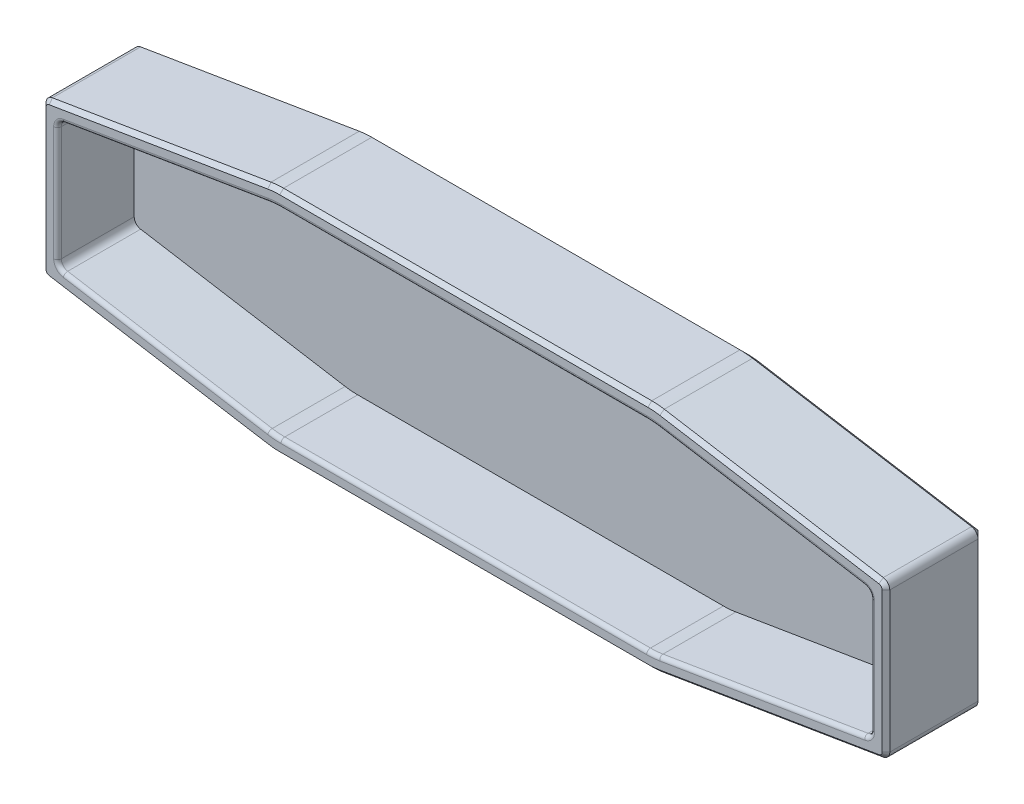
SolidWorks part; units mm, degrees
material "moto_black"
ref_plane "Front Plane" through (0, 0, 0) normal (0, 0, 1) x (1, 0, 0)
ref_plane "Top Plane" through (0, 0, 0) normal (0, 1, 0) x (1, 0, 0)
ref_plane "Right Plane" through (0, 0, 0) normal (1, 0, 0) x (0, 0, -1)
sketch "Sketch1" plane through (0, 0, 0) normal (0, 0, 1) x (1, 0, 0)
  line L12 (-24.854, 15) -> (-55, 10)
  line L14 (55, 10) -> (24.7913, 15)
  line L16 (-24.854, 15) -> (24.7913, 15)
  line L25 (0, 0) -> (4.6771, 0)
  line L26 (55, -10) -> (24.7913, -15)
  line L27 (-24.854, -15) -> (24.7913, -15)
  line L28 (-24.854, -15) -> (-55, -10)
  line L29 (-24.6892, 13) -> (-53, 8.3044)
  line L30 (-53, 8.3044) -> (-53, -8.3044)
  line L31 (-24.6892, -13) -> (-53, -8.3044)
  line L32 (-24.6892, -13) -> (24.6269, -13)
  line L33 (53, -8.3038) -> (24.6269, -13)
  line L34 (53, 8.3038) -> (53, -8.3038)
  line L35 (53, 8.3038) -> (24.6269, 13)
  line L36 (-55, 10) -> (-55, -10)
  line L37 (55, 10) -> (55, -10)
  line L38 (-24.6892, 13) -> (24.6269, 13)
  line L39 (-24.6069, 12) -> (-52, 7.4566)
  line L40 (-52, 7.4566) -> (-52, -7.4566)
  line L41 (-24.6069, -12) -> (-52, -7.4566)
  line L42 (-24.6069, -12) -> (24.5447, -12)
  line L43 (52, -7.4557) -> (24.5447, -12)
  line L44 (52, 7.4557) -> (52, -7.4557)
  line L45 (52, 7.4557) -> (24.5447, 12)
  line L46 (-24.6069, 12) -> (24.5447, 12)
  line L47 (-24.6069, 12) -> (-24.6069, -12)
  line L48 (6.6929, 12) -> (6.6929, -12)
  line L49 (-23.6069, 12) -> (-23.6069, -12)
  line L50 (-25.6069, 11.8341) -> (-25.6069, -11.8341)
  line L51 (0, 0) -> (0, 3.5519)
  line L52 (-7.6929, 12) -> (-7.6929, -12)
  line L53 (-8.6929, 12) -> (-8.6929, -12)
  line L54 (-9.6929, 12) -> (-9.6929, -12)
  line L55 (-10.6929, 12) -> (-10.6929, -12)
  line L56 (-11.6929, 12) -> (-11.6929, -12)
  line L57 (-12.6929, 12) -> (-12.6929, -12)
  line L58 (-13.6929, 12) -> (-13.6929, -12)
  line L59 (-14.6929, 12) -> (-14.6929, -12)
  line L60 (-15.6929, 12) -> (-15.6929, -12)
  line L61 (-16.6929, 12) -> (-16.6929, -12)
  line L62 (-17.6929, 12) -> (-17.6929, -12)
  line L63 (-18.6929, 12) -> (-18.6929, -12)
  line L64 (-19.6929, 12) -> (-19.6929, -12)
  line L65 (-20.6929, 12) -> (-20.6929, -12)
  line L66 (-21.6929, 12) -> (-21.6929, -12)
  line L67 (-22.6929, 12) -> (-22.6929, -12)
  line L68 (-26.6069, 11.6683) -> (-26.6069, -11.6683)
  line L69 (-27.6069, 11.5024) -> (-27.6069, -11.5024)
  line L70 (-28.6069, 11.3366) -> (-28.6069, -11.3366)
  line L71 (-29.6069, 11.1707) -> (-29.6069, -11.1707)
  line L72 (-30.6069, 11.0048) -> (-30.6069, -11.0048)
  line L73 (-31.6069, 10.839) -> (-31.6069, -10.839)
  line L74 (-32.6069, 10.6731) -> (-32.6069, -10.6731)
  line L75 (-33.6069, 10.5073) -> (-33.6069, -10.5073)
  line L76 (-34.6069, 10.3414) -> (-34.6069, -10.3414)
  line L77 (-35.6069, 10.1755) -> (-35.6069, -10.1755)
  line L78 (-36.6069, 10.0097) -> (-36.6069, -10.0097)
  line L79 (-37.6069, 9.8438) -> (-37.6069, -9.8438)
  line L80 (-38.6069, 9.678) -> (-38.6069, -9.678)
  line L81 (-39.6069, 9.5121) -> (-39.6069, -9.5121)
  line L82 (-40.6069, 9.3463) -> (-40.6069, -9.3463)
  line L83 (-41.6069, 9.1804) -> (-41.6069, -9.1804)
  line L84 (-42.6069, 9.0145) -> (-42.6069, -9.0145)
  line L85 (-43.6069, 8.8487) -> (-43.6069, -8.8487)
  line L86 (-44.6069, 8.6828) -> (-44.6069, -8.6828)
  line L87 (-45.6069, 8.517) -> (-45.6069, -8.517)
  line L88 (-46.6069, 8.3511) -> (-46.6069, -8.3511)
  line L89 (-47.6069, 8.1852) -> (-47.6069, -8.1852)
  line L90 (-48.6069, 8.0194) -> (-48.6069, -8.0194)
  line L91 (-49.6069, 7.8535) -> (-49.6069, -7.8535)
  line L92 (-50.6069, 7.6877) -> (-50.6069, -7.6877)
  line L93 (-51.6069, 7.5218) -> (-51.6069, -7.5218)
  line L94 (-6.6929, 12) -> (-6.6929, -12)
  line L95 (-5.6929, 12) -> (-5.6929, -12)
  line L96 (-4.6929, 12) -> (-4.6929, -12)
  line L97 (-3.6929, 12) -> (-3.6929, -12)
  line L98 (-2.6929, 12) -> (-2.6929, -12)
  line L99 (-1.6929, 12) -> (-1.6929, -12)
  line L100 (-0.6929, 12) -> (-0.6929, -12)
  line L101 (5.6929, 12) -> (5.6929, -12)
  line L102 (4.6929, 12) -> (4.6929, -12)
  line L103 (3.6929, 12) -> (3.6929, -12)
  line L104 (24.6069, 12) -> (-24.5447, 12)
  line L105 (-52, 7.4557) -> (-24.5447, 12)
  line L106 (-52, 7.4557) -> (-52, -7.4557)
  line L107 (-52, -7.4557) -> (-24.5447, -12)
  line L108 (24.6069, -12) -> (-24.5447, -12)
  line L109 (24.6069, -12) -> (52, -7.4566)
  line L110 (52, 7.4566) -> (52, -7.4566)
  line L111 (24.6069, 12) -> (52, 7.4566)
  line L112 (2.6929, 12) -> (2.6929, -12)
  line L113 (1.6929, 12) -> (1.6929, -12)
  line L114 (0.6929, 12) -> (0.6929, -12)
  line L115 (7.6929, 12) -> (7.6929, -12)
  line L116 (8.6929, 12) -> (8.6929, -12)
  line L117 (9.6929, 12) -> (9.6929, -12)
  line L118 (10.6929, 12) -> (10.6929, -12)
  line L119 (11.6929, 12) -> (11.6929, -12)
  line L120 (12.6929, 12) -> (12.6929, -12)
  line L121 (13.6929, 12) -> (13.6929, -12)
  line L122 (14.6929, 12) -> (14.6929, -12)
  line L123 (15.6929, 12) -> (15.6929, -12)
  line L124 (16.6929, 12) -> (16.6929, -12)
  line L125 (17.6929, 12) -> (17.6929, -12)
  line L126 (18.6929, 12) -> (18.6929, -12)
  line L127 (19.6929, 12) -> (19.6929, -12)
  line L128 (20.6929, 12) -> (20.6929, -12)
  line L129 (21.6929, 12) -> (21.6929, -12)
  line L130 (22.6929, 12) -> (22.6929, -12)
  line L131 (23.6069, 12) -> (23.6069, -12)
  line L132 (24.6069, 12) -> (24.6069, -12)
  line L133 (25.6069, 11.8341) -> (25.6069, -11.8341)
  line L134 (26.6069, 11.6683) -> (26.6069, -11.6683)
  line L135 (27.6069, 11.5024) -> (27.6069, -11.5024)
  line L136 (28.6069, 11.3366) -> (28.6069, -11.3366)
  line L137 (29.6069, 11.1707) -> (29.6069, -11.1707)
  line L138 (30.6069, 11.0048) -> (30.6069, -11.0048)
  line L139 (31.6069, 10.839) -> (31.6069, -10.839)
  line L140 (32.6069, 10.6731) -> (32.6069, -10.6731)
  line L141 (33.6069, 10.5073) -> (33.6069, -10.5073)
  line L142 (34.6069, 10.3414) -> (34.6069, -10.3414)
  line L143 (35.6069, 10.1755) -> (35.6069, -10.1755)
  line L144 (36.6069, 10.0097) -> (36.6069, -10.0097)
  line L145 (37.6069, 9.8438) -> (37.6069, -9.8438)
  line L146 (38.6069, 9.678) -> (38.6069, -9.678)
  line L147 (39.6069, 9.5121) -> (39.6069, -9.5121)
  line L148 (40.6069, 9.3463) -> (40.6069, -9.3463)
  line L149 (41.6069, 9.1804) -> (41.6069, -9.1804)
  line L150 (42.6069, 9.0145) -> (42.6069, -9.0145)
  line L151 (43.6069, 8.8487) -> (43.6069, -8.8487)
  line L152 (44.6069, 8.6828) -> (44.6069, -8.6828)
  line L153 (45.6069, 8.517) -> (45.6069, -8.517)
  line L154 (46.6069, 8.3511) -> (46.6069, -8.3511)
  line L155 (47.6069, 8.1852) -> (47.6069, -8.1852)
  line L156 (48.6069, 8.0194) -> (48.6069, -8.0194)
  line L157 (49.6069, 7.8535) -> (49.6069, -7.8535)
  line L158 (50.6069, 7.6877) -> (50.6069, -7.6877)
  line L159 (51.6069, 7.5218) -> (51.6069, -7.5218)
  point P3 (-55, 0)
  point P7 (55, 0)
  dimension "D1" = 10
  dimension "D2" = 10
  dimension "D3" = 15
  dimension "D4" = 2
  dimension "D5" = 1
  dimension "D6" = 1
  dimension "D7" = 1
  dimension "D8" = 1
  dimension "D9" = 1
  dimension "D10" = 1
  dimension "D11" = 1
  dimension "D12" = 1
  dimension "D13" = 1
  dimension "D14" = 1
  dimension "D15" = 1
  dimension "D16" = 1
  dimension "D17" = 1
  dimension "D18" = 1
  dimension "D19" = 1
  dimension "D20" = 1
  dimension "D21" = 1
  dimension "D22" = 1
  dimension "D23" = 1
  dimension "D24" = 1
  dimension "D25" = 1
  dimension "D26" = 1
  dimension "D27" = 1
  dimension "1" = 1
  dimension "D28" = 1
  dimension "D29" = 1
  dimension "D30" = 1
  dimension "D31" = 1
  dimension "D32" = 1
  dimension "D33" = 1
  dimension "D34" = 1
  dimension "D35" = 1
  dimension "D36" = 1
  dimension "D37" = 1
  dimension "D38" = 1
  dimension "D39" = 1
  dimension "D40" = 1
  dimension "D41" = 1
  dimension "D42" = 1
  dimension "D43" = 1
  dimension "D44" = 1
  dimension "D45" = 1
  dimension "D46" = 1
  dimension "D47" = 1
  dimension "D48" = 1
  dimension "D49" = 1
  dimension "D50" = 1
  dimension "D51" = 1
  dimension "D52" = 1
  dimension "D54" = 1
  dimension "D55" = 1
extrude "Boss-Extrude1" add sketch "Sketch1" against normal blind 3 contours L37 L14 L16 L12 L36 L28 L27 L26 L29 L38 L35 L34 L33 L32 L31 L30 region at (-0.0314, 13.8598, 0)
sketch "Sketch3" plane through (0, 0, 0) normal (0, 0, 1) x (1, 0, 0)
  line L44 (-53, 8.3044) -> (-53, -8.3044)
  line L45 (-53, -8.3044) -> (-24.6892, -13)
  line L46 (-24.6892, -13) -> (24.6269, -13)
  line L47 (24.6269, -13) -> (53, -8.3038)
  line L48 (53, -8.3038) -> (53, 8.3038)
  line L49 (53, 8.3038) -> (24.6269, 13)
  line L50 (24.6269, 13) -> (-24.6892, 13)
  line L51 (-24.6892, 13) -> (-53, 8.3044)
  line L52 (-53, 8.3044) -> (-53, -8.3044)
  line L53 (-53, -8.3044) -> (-24.6892, -13)
  line L54 (-24.6892, -13) -> (24.6269, -13)
  line L55 (24.6269, -13) -> (53, -8.3038)
  line L56 (53, -8.3038) -> (53, 8.3038)
  line L57 (53, 8.3038) -> (24.6269, 13)
  line L58 (24.6269, 13) -> (-24.6892, 13)
  line L59 (-24.6892, 13) -> (-53, 8.3044)
  dimension "D1" = 0
extrude "Boss-Extrude2" add sketch "Sketch3" against normal blind 3
extrude "Boss-Extrude3" add sketch "Sketch1<4>" along normal blind 10 contours L37 L14 L16 L12 L36 L28 L27 L26 L29 L38 L35 L34 L33 L32 L31 L30 region at (-0.0314, 13.8598, 0)
sketch "Sketch1<4>" plane through (0, 0, 0) normal (0, 0, 1) x (1, 0, 0) same geometry as "Sketch1"
fillet "Fillet1" radius 10 8 edges at (24.7913, -15, 3.5) (24.6269, -13, 5) (24.7913, 15, 3.5) (24.6269, 13, 5) (-24.6892, 13, 5) (-24.854, 15, 3.5) (-24.6892, -13, 5) (-24.854, -15, 3.5)
fillet "Fillet2" radius 1 8 edges at (55, 10, 3.5) (55, -10, 3.5) (53, -8.3038, 5) (53, 8.3038, 5) (-53, 8.3044, 5) (-55, 10, 3.5) (-53, -8.3044, 5) (-55, -10, 3.5)
chamfer "Chamfer1" distance 1 angle 45 16 edges at (24.7885, 14.9664, -3) (-0.0305, 15, -3) (-24.8512, 14.9662, -3) (-39.9151, 12.502, -3) (-54.7628, 9.7989, -3) (-55, 0, -3) (-54.7628, -9.7989, -3) (-39.9151, -12.502, -3) (-24.8512, -14.9662, -3) (-0.0305, -15, -3) (24.7885, -14.9664, -3) (39.8828, -12.5021, -3) (54.7627, -9.7987, -3) (55, 0, -3) (54.7627, 9.7987, -3) (39.8828, 12.5021, -3)
chamfer "Chamfer2" distance 0.5 angle 45 16 edges at (-54.7628, -9.7989, 10) (-39.9151, -12.502, 10) (-55, 0, 10) (-24.8512, -14.9662, 10) (-54.7628, 9.7989, 10) (-0.0305, -15, 10) (-39.9151, 12.502, 10) (24.7885, -14.9664, 10) (-24.8512, 14.9662, 10) (39.8828, -12.5021, 10) (-0.0305, 15, 10) (54.7627, -9.7987, 10) (24.7885, 14.9664, 10) (55, 0, 10) (54.7627, 9.7987, 10) (39.8828, 12.5021, 10)
fillet "Fillet4" radius 0.5 16 edges at (-24.6865, 12.9662, 10) (-38.8327, 10.6542, 10) (-52.7628, 8.1033, 10) (-53, 0, 10) (-52.7628, -8.1033, 10) (-38.8327, -10.6542, 10) (-24.6865, -12.9662, 10) (-0.0303, -13, 10) (24.6241, -12.9664, 10) (38.8006, -10.654, 10) (52.7627, -8.1025, 10) (53, 0, 10) (52.7627, 8.1025, 10) (38.8006, 10.654, 10) (24.6241, 12.9664, 10) (-0.0303, 13, 10)
